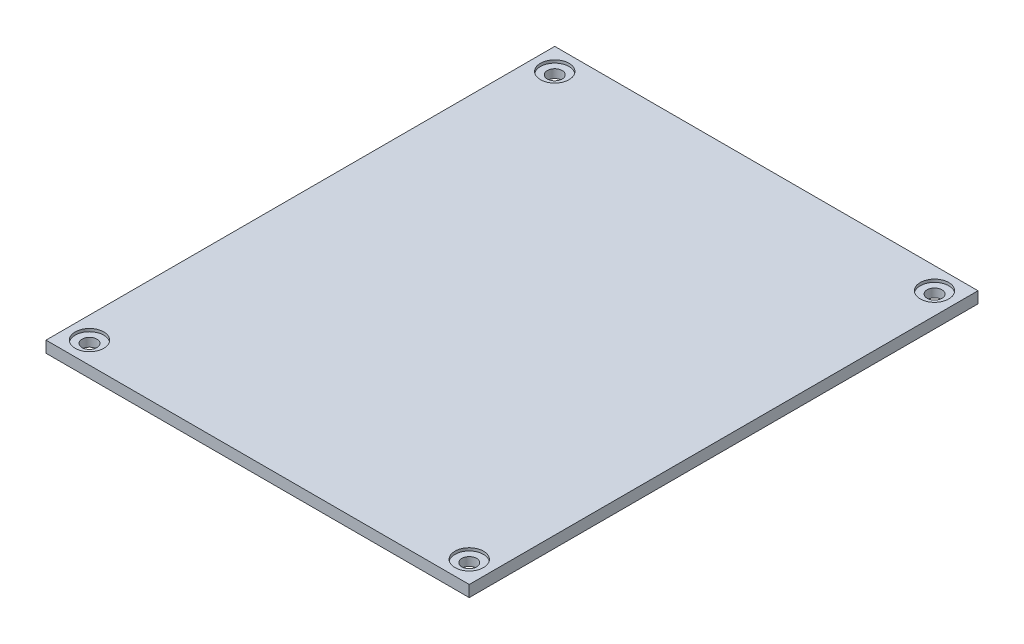
SolidWorks part; units mm, degrees
ref_plane "Front Plane" through (0, 0, 0) normal (0, 0, 1) x (1, 0, 0)
ref_plane "Top Plane" through (0, 0, 0) normal (0, 1, 0) x (1, 0, 0)
ref_plane "Right Plane" through (0, 0, 0) normal (1, 0, 0) x (0, 0, -1)
sketch "Sketch1" plane through (0, 0, 0) normal (0, 1, 0) x (1, 0, 0)
  line L1 (-37.084, 44.577) -> (37.084, 44.577)
  line L2 (-37.084, 44.577) -> (-37.084, -44.577)
  line L3 (-37.084, -44.577) -> (37.084, -44.577)
  line L4 (37.084, 44.577) -> (37.084, -44.577)
  circle A0 centre (-33.274, 40.767) radius 1.3
  circle A1 centre (33.274, 40.767) radius 1.3
  circle A2 centre (33.274, -40.767) radius 1.3
  circle A3 centre (-33.274, -40.767) radius 1.3
  circle A4 centre (-33.274, 40.767) radius 2.5
  circle A5 centre (33.274, 40.767) radius 2.5
  circle A6 centre (33.274, -40.767) radius 2.5
  circle A7 centre (-33.274, -40.767) radius 2.5
  point P4 (0, 44.577)
  point P6 (-37.084, 0)
  dimension "D3" = 2.6
  dimension "D4" = 2.6
  dimension "D5" = 2.6
  dimension "D6" = 2.6
  dimension "D15" = 5
  dimension "D16" = 5
  dimension "D17" = 5
  dimension "D18" = 5
  dimension "D1" = 74.168
  dimension "D2" = 89.154
  dimension "D7" = 3.81
  dimension "D8" = 3.81
  dimension "D9" = 3.81
  dimension "D10" = 3.81
  dimension "D11" = 3.81
  dimension "D12" = 3.81
  dimension "D13" = 3.81
  dimension "D14" = 3.81
extrude "Boss-Extrude2" add sketch "Sketch1" along normal blind 2 contours L4 L1 L2 L3 A7 A6 A5 A4 region at (0, 0, 0)
extrude "Boss-Extrude3" add sketch "Sketch1<3>" along normal blind 1.5 contours A4 A0 | A5 A1 | A7 A3 | A6 A2 region at (-35.7033, 0, -40.767) region at (30.8447, 0, -40.767) region at (30.8447, 0, 40.767) region at (-35.7033, 0, 40.767)
sketch "Sketch1<3>" plane through (0, 0, 0) normal (0, 1, 0) x (1, 0, 0) same geometry as "Sketch1"
